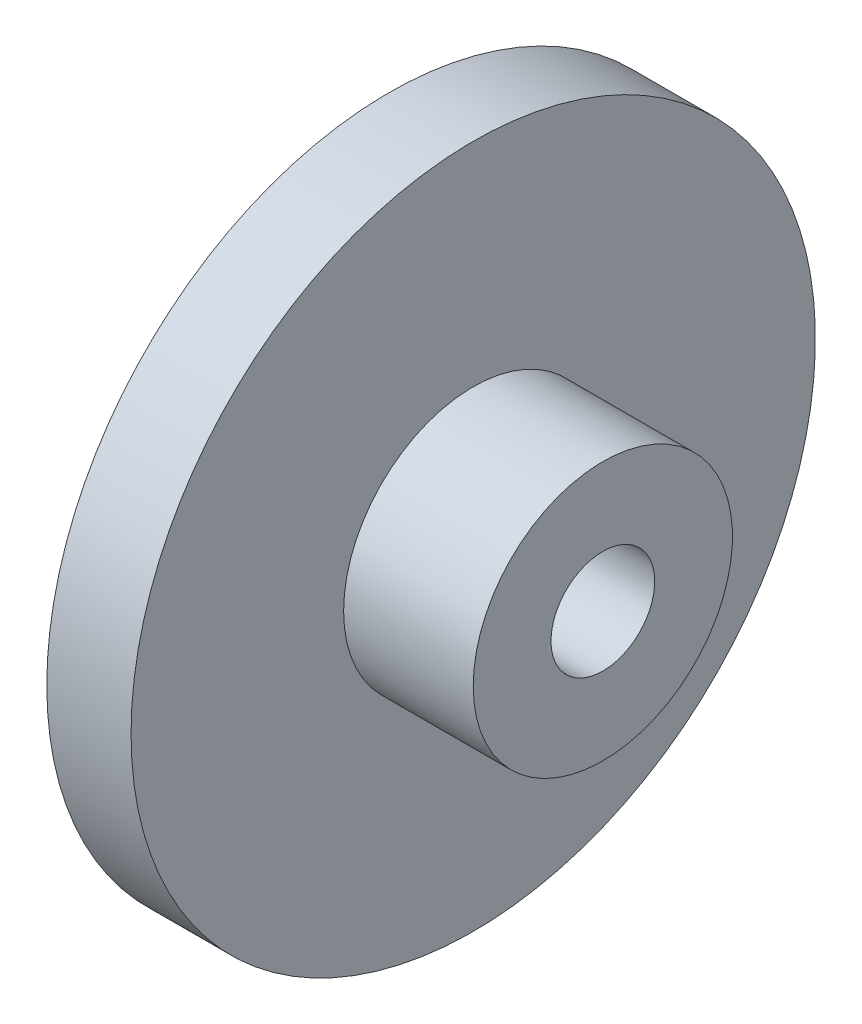
SolidWorks part; units mm, degrees
material "Brass"
ref_plane "Front Plane" through (0, 0, 0) normal (0, 0, 1) x (1, 0, 0)
ref_plane "Top Plane" through (0, 0, 0) normal (0, 1, 0) x (1, 0, 0)
ref_plane "Right Plane" through (0, 0, 0) normal (1, 0, 0) x (0, 0, -1)
sketch "Sketch1" plane through (0, 0, 0) normal (0, 1, 0) x (1, 0, 0)
  line L0 (-31.6089, 0) -> (66.0175, 0) construction
  line L3 (0, 4) -> (0, 26.4)
  line L4 (0, 26.4) -> (6.5, 26.4)
  line L5 (6.5, 26.4) -> (6.5, 10)
  line L6 (6.5, 10) -> (16.5, 10)
  line L7 (16.5, 10) -> (16.5, 4)
  line L8 (16.5, 4) -> (0, 4)
  dimension "D1" = 26.4
  dimension "D2" = 4
  dimension "D3" = 10
  dimension "D4" = 10
  dimension "D5" = 16.5
revolve "Revolve1" add sketch "Sketch1" angle 360 about L0
